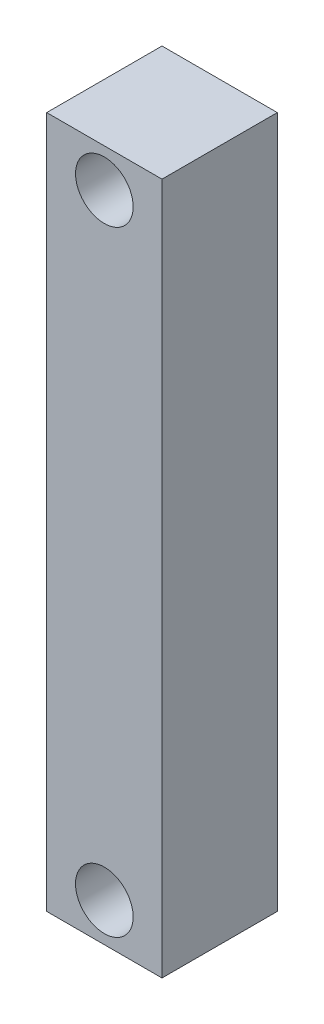
SolidWorks part; units mm, degrees
ref_plane "前视基准面" through (0, 0, 0) normal (0, 0, 1) x (1, 0, 0)
ref_plane "上视基准面" through (0, 0, 0) normal (0, 1, 0) x (1, 0, 0)
ref_plane "右视基准面" through (0, 0, 0) normal (1, 0, 0) x (0, 0, -1)
other "Configuration Table"
sketch "草图1" plane through (0, 0, 0) normal (0, 0, 1) x (1, 0, 0)
  line L1 (3, -18) -> (-3, -18)
  line L2 (3, -18) -> (3, 18)
  line L3 (3, 18) -> (-3, 18)
  line L4 (-3, -18) -> (-3, 18)
  line L5 (3, -18) -> (-3, 18) construction
  line L6 (3, 18) -> (-3, -18) construction
  point P0 (0, 0)
  dimension "D1" = 36
  dimension "D2" = 6
extrude "凸台-拉伸1" add sketch "草图1" along normal blind 6
sketch "草图2" plane through (0, 0, 6) normal (0, 0, 1) x (1, 0, 0)
  line L0 (0, 0) -> (0, 16) construction
  line L1 (0, 0) -> (3, 0) construction
  line L2 (3, -18) -> (3, 18) construction
  circle A0 centre (0, 16) radius 1.5
  circle A1 centre (0, -16) radius 1.5
  dimension "D2" = 3
  dimension "D1" = 16
extrude "切除-拉伸1" cut sketch "草图2" against normal blind 6
